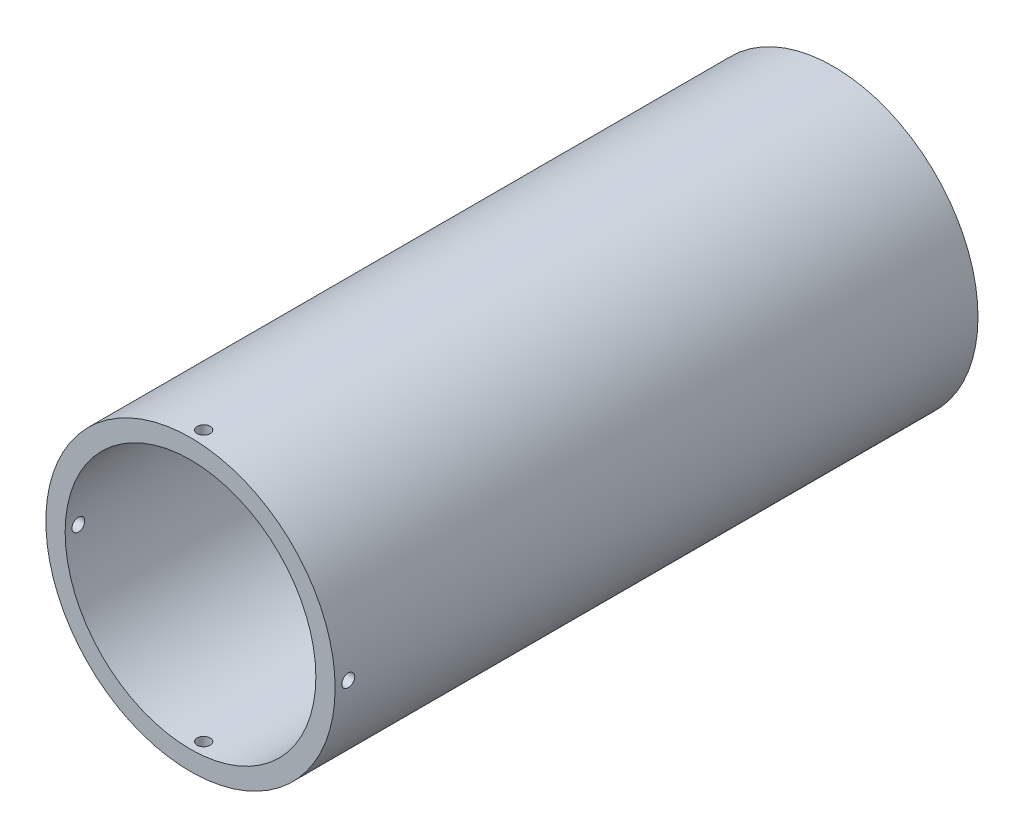
SolidWorks part; units mm, degrees
ref_plane "Спереди" through (0, 0, 0) normal (0, 0, 1) x (1, 0, 0)
ref_plane "Сверху" through (0, 0, 0) normal (0, 1, 0) x (1, 0, 0)
ref_plane "Справа" through (0, 0, 0) normal (1, 0, 0) x (0, 0, -1)
sketch "Эскиз1" plane through (0, 0, 0) normal (0, 0, 1) x (1, 0, 0)
  circle A0 centre (0, 0) radius 22.5
  circle A1 centre (0, 0) radius 19.5
  dimension "D1" = 45
  dimension "D2" = 39
extrude "Бобышка-Вытянуть1" add sketch "Эскиз1" along normal blind 100
sketch "Эскиз2" plane through (0, 0, 100) normal (0, 0, 1) x (1, 0, 0)
  line L0 (0, 22.5) -> (0, -22.5) construction
  circle A0 centre (0, 0) radius 22.5 construction
ref_plane "Плоскость1" through (0, 22.5, 0) normal (0, 1, 0) x (1, 0, 0)
sketch "Эскиз3" plane through (0, 22.5, 0) normal (0, 1, 0) x (1, 0, 0)
  line L0 (0, -99.9463) -> (0, -83.414) construction
  circle A0 centre (0, -97.9463) radius 1
  dimension "D1" = 2
  dimension "D2" = 2
extrude "Вырез-Вытянуть1" cut sketch "Эскиз3" against normal blind 25
pattern_circular "Круговой массив1" count 4 over 360 about axis through (0, 0, 100) along (0, 0, -1) of "Вырез-Вытянуть1"
